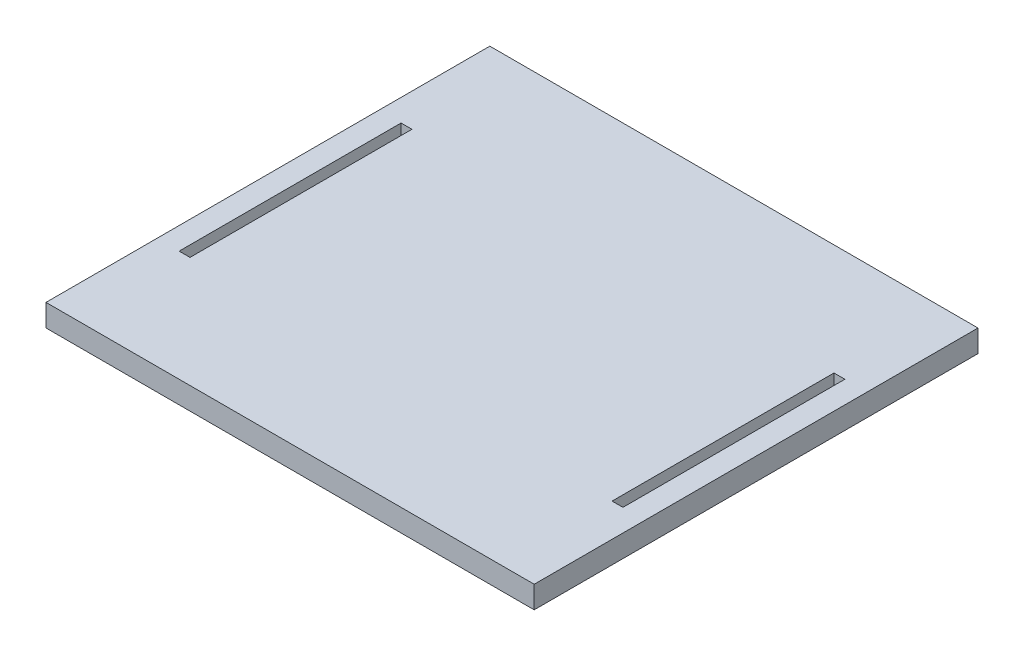
SolidWorks part; units mm, degrees
ref_plane "Alzado" through (0, 0, 0) normal (0, 0, 1) x (1, 0, 0)
ref_plane "Planta" through (0, 0, 0) normal (0, 1, 0) x (1, 0, 0)
ref_plane "Vista lateral" through (0, 0, 0) normal (1, 0, 0) x (0, 0, -1)
sketch "Croquis1" plane through (0, 0, 0) normal (0, 1, 0) x (1, 0, 0)
  line L0 (-110, 0) -> (110, 0) construction
  line L1 (-110, -100) -> (110, -100)
  line L2 (-110, -100) -> (-110, 100)
  line L3 (-110, 100) -> (110, 100)
  line L4 (110, -100) -> (110, 100)
  line L5 (-110, -100) -> (110, 100) construction
  line L6 (-110, 100) -> (110, -100) construction
  line L8 (-100, -50) -> (-95.1, -50)
  line L9 (-100, -50) -> (-100, 50)
  line L10 (-100, 50) -> (-95.1, 50)
  line L11 (-95.1, -50) -> (-95.1, 50)
  line L12 (-100, -50) -> (-95.1, 50) construction
  line L13 (-100, 50) -> (-95.1, -50) construction
  line L14 (95.1, -50) -> (100, -50)
  line L15 (95.1, -50) -> (95.1, 50)
  line L16 (95.1, 50) -> (100, 50)
  line L17 (100, -50) -> (100, 50)
  line L18 (95.1, -50) -> (100, 50) construction
  line L19 (95.1, 50) -> (100, -50) construction
  point P0 (0, 0)
  point P8 (-97.55, 0)
  point P13 (97.55, 0)
  dimension "D1" = 200
  dimension "D2" = 220
  dimension "D3" = 100
  dimension "D4" = 10
  dimension "D5" = 4.9
  dimension "D6" = 4.9
  dimension "D7" = 10
extrude "Saliente-Extruir1" add sketch "Croquis1" along normal blind 10
